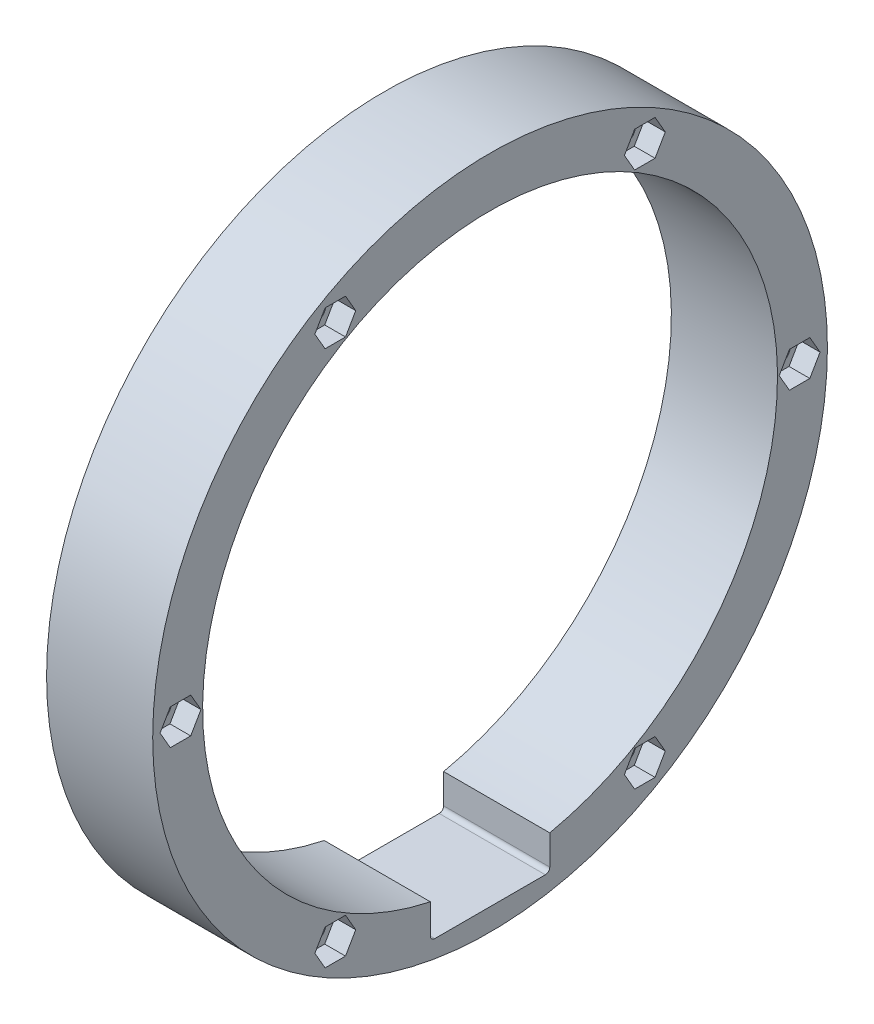
SolidWorks part; units mm, degrees
ref_plane "Front Plane" through (0, 0, 0) normal (0, 0, 1) x (1, 0, 0)
ref_plane "Top Plane" through (0, 0, 0) normal (0, 1, 0) x (1, 0, 0)
ref_plane "Right Plane" through (0, 0, 0) normal (1, 0, 0) x (0, 0, -1)
sketch "Sketch1" plane through (0, 0, 0) normal (1, 0, 0) x (0, 0, -1)
  circle A0 centre (0, 0) radius 76.29
  circle A1 centre (0, 0) radius 65
  dimension "D1" = 152.58
  dimension "D2" = 130
extrude "Boss-Extrude1" add sketch "Sketch1" along normal blind 24
sketch "Sketch2" plane through (24, 0, 0) normal (1, 0, 0) x (0, 0, -1)
  line L0 (0, -34.8517) -> (0, -97.703) construction
  line L1 (-13.5, -51.894) -> (13.5, -51.894)
  line L2 (-13.5, -51.894) -> (-13.5, -70.29)
  line L3 (-12.5, -71.29) -> (12.5, -71.29)
  line L4 (13.5, -51.894) -> (13.5, -70.29)
  circle A1 centre (0, 0) radius 76.29 construction
  arc A2 (-13.5, -70.29) -> (-12.5, -71.29) centre (-12.5, -70.29) ccw
  arc A3 (13.5, -70.29) -> (12.5, -71.29) centre (12.5, -70.29) cw
  point P6 (0, -51.894)
  point P10 (0, -76.29)
  dimension "D2" = 1
  dimension "D3" = 1
  dimension "D1" = 5
  dimension "D4" = 27
extrude "Cut-Extrude1" cut sketch "Sketch2" against normal up to next
sketch "Sketch3" plane through (24, 0, 0) normal (1, 0, 0) x (0, 0, -1)
  line L0 (-94.7404, 0) -> (95.285, 0) construction
  circle A0 centre (-70, 0) radius 2.65
  circle A1 centre (-35, 60.6218) radius 2.65
  circle A2 centre (35, 60.6218) radius 2.65
  circle A3 centre (70, 0) radius 2.65
  circle A4 centre (35, -60.6218) radius 2.65
  circle A5 centre (-35, -60.6218) radius 2.65
  point P17 (0, 0)
  dimension "D1" = 5.3
  dimension "D2" = 70
  dimension "D3" = 6
extrude "Cut-Extrude2" cut sketch "Sketch3" against normal up to next
sketch "Sketch4" plane through (24, 0, 0) normal (1, 0, 0) x (0, 0, -1)
  line L0 (-37.3094, 56.6218) -> (-32.6906, 56.6218)
  line L1 (-67.6906, -4) -> (-65.3812, 0)
  line L2 (-65.3812, 0) -> (-67.6906, 4)
  line L3 (-67.6906, 4) -> (-72.3094, 4)
  line L4 (-72.3094, 4) -> (-74.6188, 0)
  line L5 (-74.6188, 0) -> (-72.3094, -4)
  line L6 (-72.3094, -4) -> (-67.6906, -4)
  line L7 (-32.6906, 56.6218) -> (-30.3812, 60.6218)
  line L8 (-30.3812, 60.6218) -> (-32.6906, 64.6218)
  line L9 (-32.6906, 64.6218) -> (-37.3094, 64.6218)
  line L10 (-37.3094, 64.6218) -> (-39.6188, 60.6218)
  line L11 (-39.6188, 60.6218) -> (-37.3094, 56.6218)
  line L12 (30.3812, 60.6218) -> (32.6906, 56.6218)
  line L13 (32.6906, 56.6218) -> (37.3094, 56.6218)
  line L14 (37.3094, 56.6218) -> (39.6188, 60.6218)
  line L15 (39.6188, 60.6218) -> (37.3094, 64.6218)
  line L16 (37.3094, 64.6218) -> (32.6906, 64.6218)
  line L17 (32.6906, 64.6218) -> (30.3812, 60.6218)
  line L18 (67.6906, 4) -> (65.3812, 0)
  line L19 (65.3812, 0) -> (67.6906, -4)
  line L20 (67.6906, -4) -> (72.3094, -4)
  line L21 (72.3094, -4) -> (74.6188, 0)
  line L22 (74.6188, 0) -> (72.3094, 4)
  line L23 (72.3094, 4) -> (67.6906, 4)
  line L24 (37.3094, -56.6218) -> (32.6906, -56.6218)
  line L25 (32.6906, -56.6218) -> (30.3812, -60.6218)
  line L26 (30.3812, -60.6218) -> (32.6906, -64.6218)
  line L27 (32.6906, -64.6218) -> (37.3094, -64.6218)
  line L28 (37.3094, -64.6218) -> (39.6188, -60.6218)
  line L29 (39.6188, -60.6218) -> (37.3094, -56.6218)
  line L30 (-30.3812, -60.6218) -> (-32.6906, -56.6218)
  line L31 (-32.6906, -56.6218) -> (-37.3094, -56.6218)
  line L32 (-37.3094, -56.6218) -> (-39.6188, -60.6218)
  line L33 (-39.6188, -60.6218) -> (-37.3094, -64.6218)
  line L34 (-37.3094, -64.6218) -> (-32.6906, -64.6218)
  line L35 (-32.6906, -64.6218) -> (-30.3812, -60.6218)
  circle A0 centre (-70, 0) radius 4 construction
  circle A1 centre (-35, 60.6218) radius 4 construction
  circle A2 centre (35, 60.6218) radius 4 construction
  circle A3 centre (70, 0) radius 4 construction
  circle A4 centre (35, -60.6218) radius 4 construction
  circle A5 centre (-35, -60.6218) radius 4 construction
  point P52 (0, 0)
  dimension "D1" = 8
  dimension "D2" = 6
extrude "Cut-Extrude3" cut sketch "Sketch4" against normal blind 4.7
